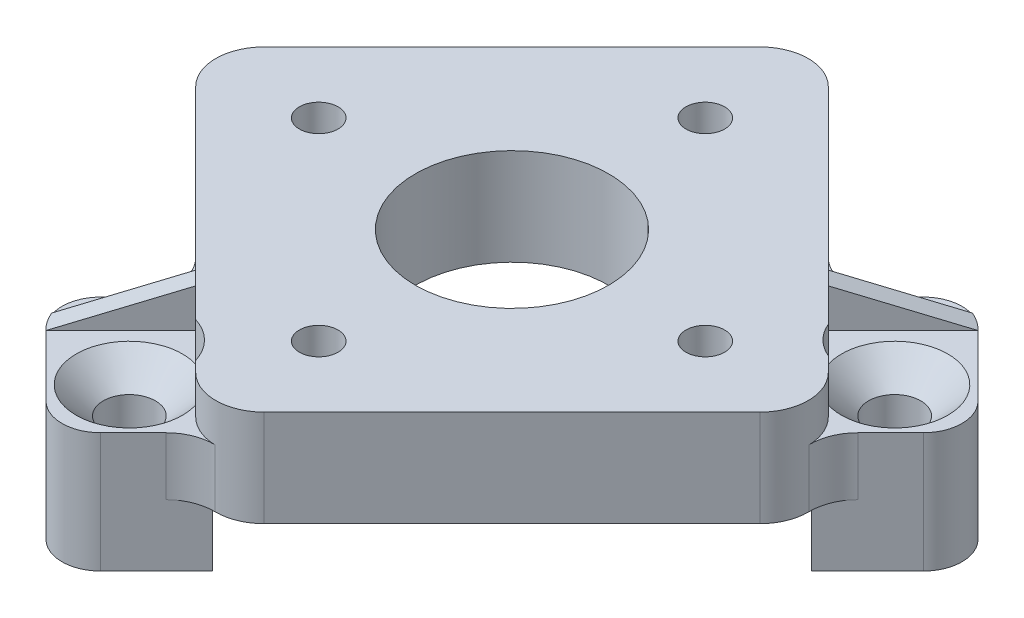
SolidWorks part; units mm, degrees
material "eSUN Tough Resin"
ref_plane "Front Plane" through (0, 0, 0) normal (0, 0, 1) x (1, 0, 0)
ref_plane "Top Plane" through (0, 0, 0) normal (0, 1, 0) x (1, 0, 0)
ref_plane "Right Plane" through (0, 0, 0) normal (1, 0, 0) x (0, 0, -1)
sketch "Sketch1" plane through (0, 0, 0) normal (0, 1, 0) x (1, 0, 0)
  line L0 (0, 10) -> (0, -10) construction
  line L1 (10, 0) -> (-10, 0) construction
  line L2 (0, 10) -> (10, 0) construction
  line L3 (10, 0) -> (0, -10) construction
  line L4 (0, -10) -> (-10, 0) construction
  line L8 (-10, 0) -> (0, 10) construction
  line L9 (1.7678, 14.5962) -> (14.5962, 1.7678)
  line L10 (14.5962, -1.7678) -> (1.7678, -14.5962)
  line L11 (-1.7678, -14.5962) -> (-14.5962, -1.7678)
  line L12 (-14.5962, 1.7678) -> (-1.7678, 14.5962)
  line L13 (16.364, 0) -> (0, -16.364) construction
  line L14 (0, -16.364) -> (-16.364, 0) construction
  line L15 (0, 16.364) -> (16.364, 0) construction
  line L16 (-16.364, 0) -> (0, 16.364) construction
  circle A7 centre (0, 10) radius 0.5
  circle A8 centre (0, -10) radius 0.5
  circle A9 centre (10, 0) radius 0.5
  circle A10 centre (-10, 0) radius 0.5
  circle A11 centre (0, 0) radius 5
  arc A12 (1.7678, -14.5962) -> (-1.7678, -14.5962) centre (0, -12.8284) cw
  arc A13 (14.5962, 1.7678) -> (14.5962, -1.7678) centre (12.8284, 0) cw
  arc A14 (-14.5962, -1.7678) -> (-14.5962, 1.7678) centre (-12.8284, 0) cw
  arc A15 (1.7678, 14.5962) -> (-1.7678, 14.5962) centre (0, 12.8284) ccw
  dimension "D2" = 1
  dimension "D3" = 10
  dimension "D4" = 4.5
  dimension "D5" = 2.5
  dimension "D1" = 20
extrude "Boss-Extrude1" add sketch "Sketch1" along normal blind 5
sketch "Sketch4" plane through (0, 0, 0) normal (0, -1, 0) x (1, 0, 0)
  circle A0 centre (0, 10) radius 3
  circle A1 centre (10, 0) radius 3
  circle A2 centre (-10, 0) radius 3
  circle A3 centre (0, -10) radius 3
  point P0 (0, 10)
  point P3 (10, 0)
  point P6 (-10, 0)
  point P9 (0, -10)
  dimension "D1" = 6
ref_plane "Plane1" through (0, -2.7, 0) normal (0, 1, 0) x (1, 0, 0)
ref_plane "Plane2" through (8.182, 0, 8.182) normal (0.7071, 0, 0.7071) x (0.7071, 0, -0.7071)
ref_plane "Plane3" through (2.5251, 0, 2.5251) normal (0.7071, 0, 0.7071) x (0.7071, 0, -0.7071)
sketch "Sketch3" plane through (0, -2.7, 0) normal (0, 1, 0) x (1, 0, 0)
  line L0 (-8.182, 8.182) -> (8.182, -8.182) construction
  line L1 (-1.7678, 14.5962) -> (-14.5962, 1.7678) construction
  line L2 (1.7678, -14.5962) -> (14.5962, -1.7678) construction
  line L3 (9.8995, 9.8995) -> (14.8492, 4.9497) construction
  line L5 (10.5375, 4.9497) -> (14.8492, 0.638)
  line L12 (14.5962, 1.7678) -> (1.7678, 14.5962) construction
  line L13 (14.8492, 0.638) -> (19.161, 4.9497)
  line L20 (0, 0) -> (9.8995, 9.8995) construction
  line L21 (14.5962, 1.7678) -> (1.7678, 14.5962) construction
  line L22 (19.161, 4.9497) -> (14.8492, 9.2615)
  line L23 (14.8492, 9.2615) -> (10.5375, 4.9497)
  line L24 (19.161, 4.9497) -> (10.5375, 4.9497) construction
  line L25 (-4.9497, -19.161) -> (-4.9497, -10.5375) construction
  line L26 (-9.8995, -9.8995) -> (-4.9497, -14.8492) construction
  line L27 (-9.2615, -14.8492) -> (-4.9497, -10.5375)
  line L28 (-4.9497, -19.161) -> (-9.2615, -14.8492)
  line L29 (-0.638, -14.8492) -> (-4.9497, -19.161)
  line L30 (-4.9497, -10.5375) -> (-0.638, -14.8492)
  line L31 (10.5375, 4.9497) -> (8.7697, 6.7175)
  line L32 (8.7697, 6.7175) -> (13.0815, 11.0293)
  line L33 (13.0815, 11.0293) -> (14.8492, 9.2615)
  line L34 (-4.9497, -10.5375) -> (-6.7175, -8.7697)
  line L35 (-6.7175, -8.7697) -> (-11.0293, -13.0815)
  line L36 (-11.0293, -13.0815) -> (-9.2615, -14.8492)
  circle A2 centre (14.8492, 4.9497) radius 1.3
  circle A3 centre (-4.9497, -14.8492) radius 1.3
  dimension "D1" = 2.6
  dimension "D2" = 7
  dimension "D3" = 3.0489
  dimension "D4" = 14
  dimension "D5" = 2.5
extrude "Boss-Extrude4" add sketch "Sketch3" along normal offset from surface 3 and the other way blind 0.5 contours L30 L27 L28 L29 A3 | L35 L36 L27 L34 | L22 L23 L5 L13 A2 | L33 L32 L31 L23 up to face at (-10, 0, 0.5)
sketch "Sketch7" plane through (2.5251, 0, 2.5251) normal (0.7071, 0, 0.7071) x (0.7071, 0, -0.7071)
  line L0 (11.5711, 5) -> (17.0489, 3)
  line L1 (-11.5711, 5) -> (-17.0489, 3)
  line L2 (-17.0489, 3) -> (-11.5711, 3)
  line L3 (-11.5711, 3) -> (-11.5711, 5)
  line L4 (11.5711, 5) -> (11.5711, 3)
  line L5 (11.5711, 3) -> (17.0489, 3)
extrude "Boss-Extrude6" add sketch "Sketch7" against normal blind 1
fillet "Fillet1" radius 2.5 4 edges at (-7.1559, 1.5, 9.2081) (9.2081, 1.5, -7.1559) (15.1468, 1.5, -0.9355) (-0.9355, 1.5, 15.1468)
fillet "Fillet2" radius 2 4 edges at (-11.0293, -0.1, 13.0815) (-4.9497, -0.1, 19.161) (13.0815, -0.1, -11.0293) (19.161, -0.1, -4.9497)
hole_wizard "Ø2.0mm Dowel Hole1" positions "Sketch4" profile "Sketch11" hole size "Ø2.0" standard "ANSI Metric"
sketch "Sketch11" plane through (0, 0, 10) normal (1, 0, 0) x (0, 0, -1)
  line L0 (0, 0) -> (0, 43.5309)
  line L1 (0, 43.5309) -> (1, 42.93)
  line L2 (1, 42.93) -> (1, 0)
  line L5 (1, 0) -> (0, 0)
  line L10 (0, 43.5309) -> (-1, 42.93) construction
  line L11 (0, -6.35) -> (0, 107.95) construction
  dimension "Hole Dia." = 2
  dimension "Hole Depth" = 42.93
  dimension "Drill Angle" = 118
sketch "Sketch12" plane through (0, 3, 0) normal (0, 1, 0) x (1, 0, 0)
  circle A0 centre (-4.9497, -14.8492) radius 2.75
  circle A1 centre (14.8492, 4.9497) radius 2.625
  dimension "D1" = 5.5
  dimension "D2" = 5.25
extrude "Cut-Extrude1" cut sketch "Sketch12" along normal blind 10
hole_wizard "CSK for M2.5 Flat Head Machine Screw1" positions "3DSketch1" profile "Sketch13" countersink size "M2.5" standard "ANSI Metric"
sketch3d "3DSketch1"
  line L0 (-4.9497, -3.2, 14.8492) -> (-4.9497, 3, 14.8492) construction
  line L1 (14.8492, -3.2, -4.9497) -> (14.8492, 3, -4.9497) construction
  point P0 (-4.9497, 3, 14.8492)
  point P4 (14.8492, 3, -4.9497)
sketch "Sketch13" plane through (-4.9497, 3, 14.8492) normal (1, 0, 0) x (0, 0, 1)
  line L0 (0, 0) -> (0, 43.7412)
  line L1 (0, 43.7412) -> (1.35, 42.93)
  line L2 (1.35, 42.93) -> (1.35, 1.4)
  line L3 (1.35, 1.4) -> (2.75, 0)
  line L5 (2.75, 0) -> (0, 0)
  line L6 (-1.35, 1.4) -> (-2.75, 0) construction
  line L10 (0, 43.7412) -> (-1.35, 42.93) construction
  line L11 (0, -6.35) -> (0, 107.95) construction
  dimension "Hole Dia." = 2.7
  dimension "Hole Depth" = 42.93
  dimension "Near C'Sink Dia." = 5.5
  dimension "Near C'Sink Angle" = 90
  dimension "Drill Angle" = 118
